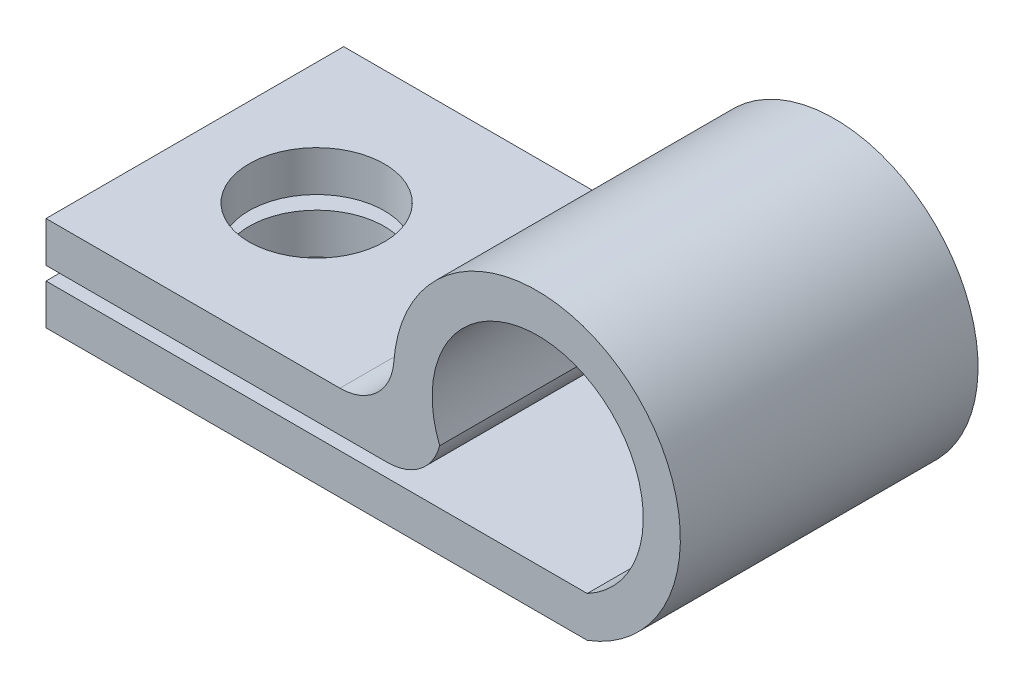
SolidWorks part; units mm, degrees
ref_plane "Front Plane" through (0, 0, 0) normal (0, 0, 1) x (1, 0, 0)
ref_plane "Top Plane" through (0, 0, 0) normal (0, 1, 0) x (1, 0, 0)
ref_plane "Right Plane" through (0, 0, 0) normal (1, 0, 0) x (0, 0, -1)
sketch "Sketch1" plane through (0, 0, 0) normal (0, 0, 1) x (1, 0, 0)
  line L1 (0, 0) -> (-20, 0)
  line L2 (0, 0) -> (0, 1.5)
  line L3 (0, 1.5) -> (-20, 1.5)
  line L4 (-20, 0) -> (-20, 1.5)
  line L5 (-20, 2) -> (-5.4538, 2)
  line L6 (-20, 2) -> (-20, 3.5)
  line L7 (-20, 3.5) -> (-5.4538, 3.5)
  line L8 (-5.4538, 2) -> (-5.4538, 3.5)
  arc A0 (-5.4538, 3.5) -> (0, 1.5) centre (-1.8308, 4.9436) cw
  arc A1 (-6.9538, 3.5) -> (0, 0) centre (-1.8597, 4.963) cw
  point P10 (-6.9538, 3.5)
  dimension "D6" = 3.9
  dimension "D7" = 1.5
  dimension "D8" = 5.3
  dimension "D1" = 20
  dimension "D2" = 1.5
  dimension "D3" = 1.5
  dimension "D4" = 0.5
  dimension "D5" = 0
  dimension "D9" = 5.4538
extrude "Boss-Extrude1" add sketch "Sketch1" along normal blind 11 contours L5 L8 L7 L6 | A1 L7 A0 L2 | L4 L1 L2 L3 region at (-10, 0.75, 0) region at (0.1475, 0.75, 0) region at (-12.7269, 2.75, 0)
ref_plane "Plane1" through (0, 0, 0) normal (0, -1, 0) x (-1, 0, 0)
sketch "Sketch2" plane through (0, 0, 0) normal (0, -1, 0) x (-1, 0, 0)
  line L0 (20, -11) -> (20, 0) construction
  line L1 (0, 0) -> (20, 0) construction
  circle A0 centre (15.5, -5.5) radius 2.5
  point P2 (20, -5.5)
  dimension "D1" = 4.5
  dimension "D2" = 5.5
extrude "Cut-Extrude1" cut sketch "Sketch2" against normal through all
fillet "Fillet1" radius 2 1 edges at (-6.9538, 3.5, 5.5)
fillet "Fillet2" radius 2 1 edges at (-5.4538, 2, 5.5)
